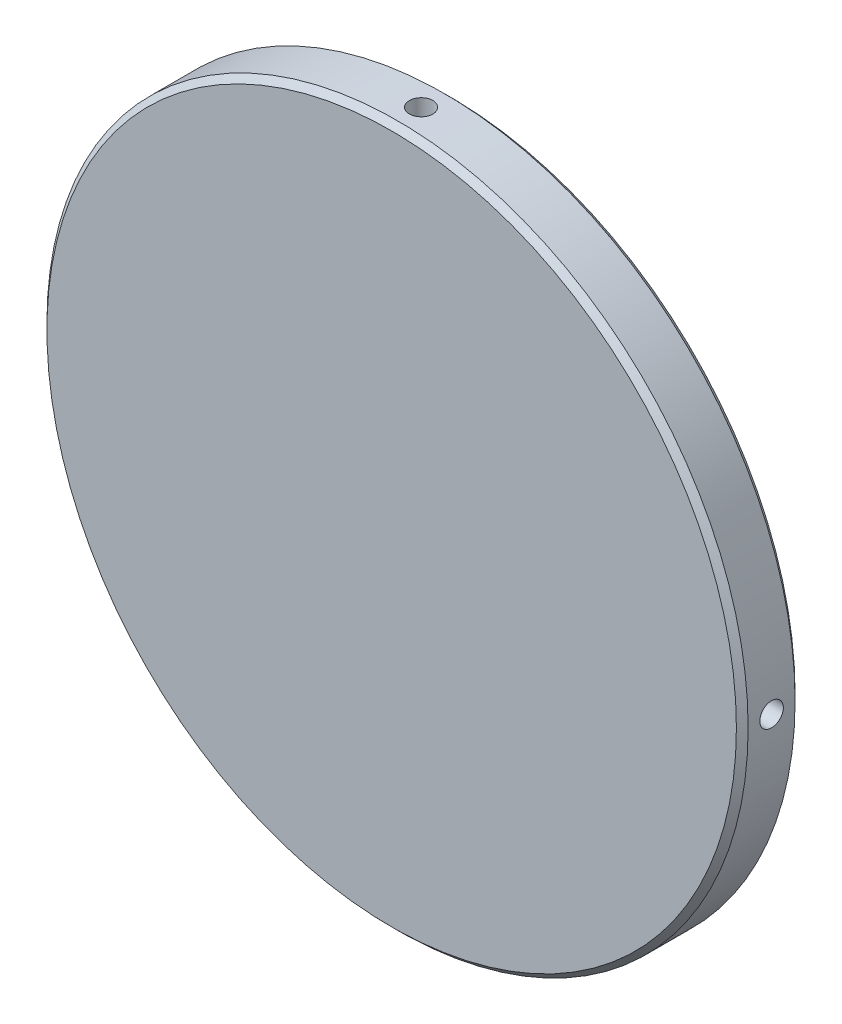
SolidWorks part; units mm, degrees
material "6063-T6"
ref_plane "Ön Düzlem" through (0, 0, 0) normal (0, 0, 1) x (1, 0, 0)
ref_plane "Üst Düzlem" through (0, 0, 0) normal (0, 1, 0) x (1, 0, 0)
ref_plane "Sağ Düzlem" through (0, 0, 0) normal (1, 0, 0) x (0, 0, -1)
sketch "Sketch1" plane through (0, 0, 0) normal (0, 0, 1) x (1, 0, 0)
  circle A0 centre (0, 0) radius 59.75
  dimension "D1" = 119.5
extrude "Boss-Extrude1" add sketch "Sketch1" along normal mid plane 10
chamfer "Chamfer1" distance 1 angle 45 2 edges at (59.75, 0, -5) (59.75, 0, 5)
sketch "Sketch2" plane through (0, 0, 0) normal (0, 1, 0) x (1, 0, 0)
  circle A0 centre (0, 0) radius 2
extrude "Cut-Extrude1" cut sketch "Sketch2" along normal blind 17 from offset 54.5
extrude "Cut-Extrude2" cut sketch "Sketch2<2>" against normal blind 17 from offset 54.5 offset against normal yes
sketch "Sketch2<2>" plane through (0, 0, 0) normal (0, 1, 0) x (1, 0, 0) same geometry as "Sketch2"
sketch "Sketch3" plane through (0, 0, 0) normal (1, 0, 0) x (0, 0, -1)
  circle A0 centre (0, 0) radius 2
extrude "Cut-Extrude3" cut sketch "Sketch3" along normal blind 16 from offset 54.5
extrude "Cut-Extrude4" cut sketch "Sketch3<2>" against normal blind 16 from offset 54.5 offset against normal yes
sketch "Sketch3<2>" plane through (0, 0, 0) normal (1, 0, 0) x (0, 0, -1) same geometry as "Sketch3"
